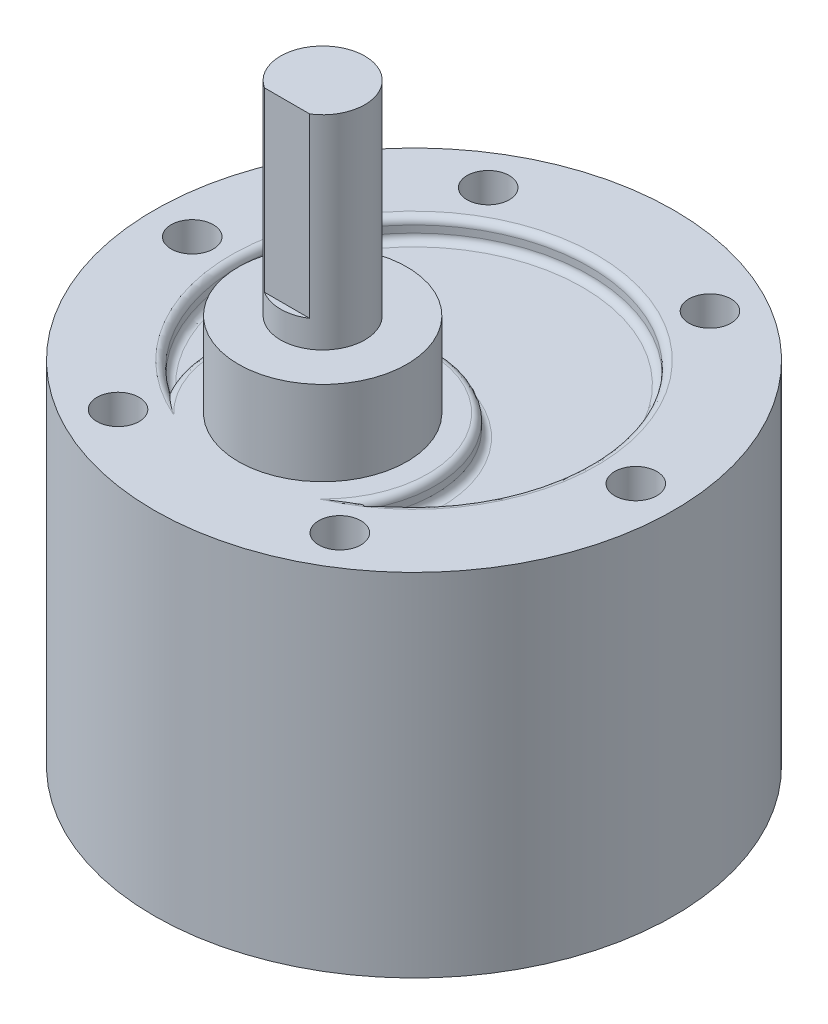
SolidWorks part; units mm, degrees
ref_plane "Alzado" through (0, 0, 0) normal (0, 0, 1) x (1, 0, 0)
ref_plane "Planta" through (0, 0, 0) normal (0, 1, 0) x (1, 0, 0)
ref_plane "Vista lateral" through (0, 0, 0) normal (1, 0, 0) x (0, 0, -1)
sketch "Croquis1" plane through (0, 0, 0) normal (0, 1, 0) x (1, 0, 0)
  circle A0 centre (0, 0) radius 18.5
  dimension "D1" = 37
extrude "Saliente-Extruir1" add sketch "Croquis1" along normal blind 25
sketch "Croquis3" plane through (0, 25, 0) normal (0, 1, 0) x (1, 0, 0)
  circle A0 centre (0, 0) radius 12.5
  dimension "D1" = 25
extrude "Cortar-Extruir2" cut sketch "Croquis3" against normal blind 1.5
sketch "Croquis4" plane through (0, 23.5, 0) normal (0, 1, 0) x (1, 0, 0)
  circle A0 centre (0, -6.5) radius 6
  circle A2 centre (0, 0) radius 12.5 construction
  circle A4 centre (0, -6.5) radius 8
  dimension "D1" = 12
  dimension "D2" = 16
extrude "Saliente-Extruir6" add sketch "Croquis4" along normal blind 1.5
sketch "Croquis5" plane through (0, 23.5, 0) normal (0, 1, 0) x (1, 0, 0)
  circle A0 centre (0, -6.5) radius 6
  arc A1 (7.0148, -10.3462) -> (-7.0148, -10.3462) centre (0, 0) ccw construction
  dimension "D1" = 12
extrude "Saliente-Extruir7" add sketch "Croquis5" along normal blind 7.5
sketch "Croquis6" plane through (0, 31, 0) normal (0, 1, 0) x (1, 0, 0)
  circle A0 centre (0, -6.5) radius 3
  circle A1 centre (0, -6.5) radius 6 construction
  dimension "D1" = 6
extrude "Saliente-Extruir8" add sketch "Croquis6" along normal blind 14.5
sketch "Croquis8" plane through (0, 25, 0) normal (0, 1, 0) x (1, 0, 0)
  line L0 (-6, -6.5) -> (-6, -17.5)
  line L1 (6, -6.5) -> (6, -17.5)
  circle A0 centre (0, -6.5) radius 6 construction
  circle A1 centre (0, -6.5) radius 6 construction
  circle A2 centre (0, 0) radius 18.5 construction
  circle A3 centre (-7.5, -13.5647) radius 1.5
  dimension "D1" = 3
  dimension "D2" = 15.5
extrude "Cortar-Extruir4" cut sketch "Croquis8" against normal blind 4 contours A3
pattern_circular "MatrizC2" count 6 over 360 about axis through (0, 0, 0) along (0, 1, 0) of "Cortar-Extruir4"
fillet "Redondeo1" radius 0.5 4 edges at (0, 23.5, -1.5) (0, 25, -1.5) (0, 23.5, -12.5) (0, 25, -12.5)
sketch "Croquis9" plane through (0, 45.5, 0) normal (0, 1, 0) x (1, 0, 0)
  line L0 (-1.61, -9.0314) -> (1.61, -9.0314)
  circle A0 centre (0, -6.5) radius 3 construction
  arc A1 (-1.61, -9.0314) -> (1.61, -9.0314) centre (0, -6.5) ccw
  dimension "D1" = 3.22
extrude "Cortar-Extruir5" cut sketch "Croquis9" against normal blind 12.6
